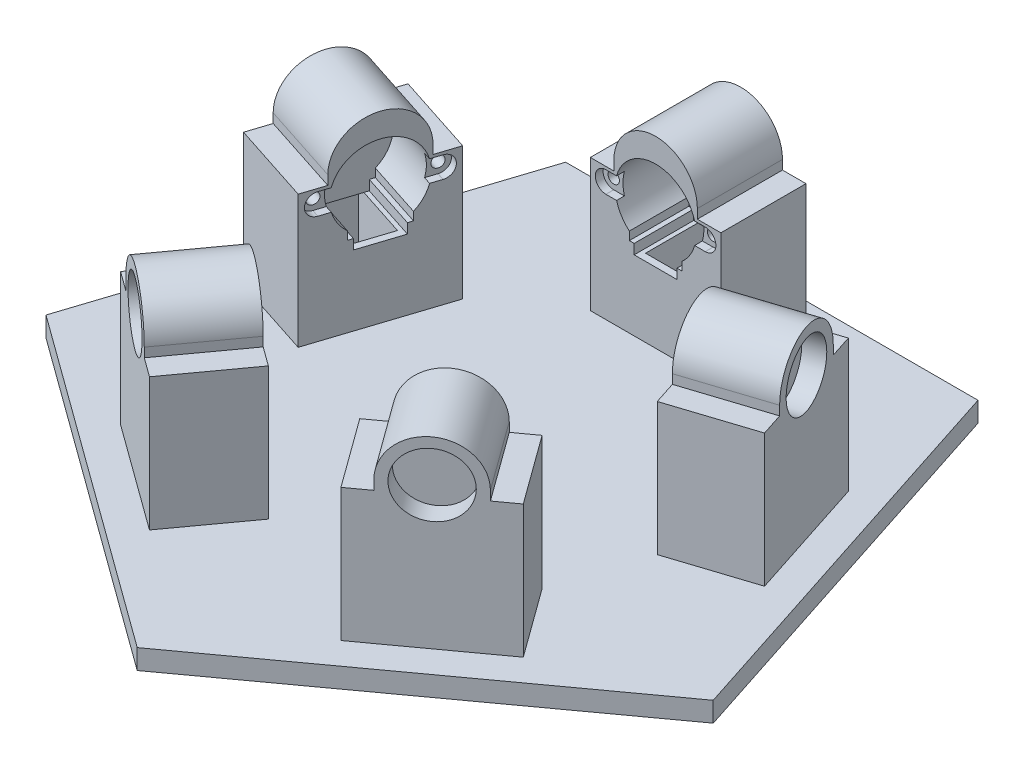
SolidWorks part; units mm, degrees
ref_plane "Front Plane" through (0, 0, 0) normal (0, 0, 1) x (1, 0, 0)
ref_plane "Top Plane" through (0, 0, 0) normal (0, 1, 0) x (1, 0, 0)
ref_plane "Right Plane" through (0, 0, 0) normal (1, 0, 0) x (0, 0, -1)
ref_plane "Psuedo R-offset" through (0, 0, -80) normal (0, 0, 1) x (1, 0, 0)
sketch "Sketch12" plane through (0, 0, 0) normal (0, 1, 0) x (1, 0, 0)
  line L1 (0, -123.6068) -> (117.5571, -38.1966)
  line L2 (117.5571, -38.1966) -> (72.6543, 100)
  line L3 (72.6543, 100) -> (-72.6543, 100)
  line L4 (-72.6543, 100) -> (-117.5571, -38.1966)
  line L5 (-117.5571, -38.1966) -> (0, -123.6068)
  line L6 (-55, 80) -> (55, 80) construction
  circle A0 centre (0, 0) radius 100 construction
  dimension "D1" = 20
extrude "Base" add sketch "Sketch12" against normal blind 7
ref_axis "Axis1" through (0, -9.448, 0) along (0, 1, 0)
sketch "Sketch2" plane through (0, 0, -80) normal (0, 0, 1) x (1, 0, 0)
  line L0 (-7.55, 28.2411) -> (-7.55, 24.75)
  line L1 (-7.55, 24.75) -> (7.55, 24.75)
  line L2 (7.55, 24.75) -> (7.55, 28.2411)
  line L3 (7.55, 28.2411) -> (9.25, 28.2411)
  line L4 (9.25, 28.2411) -> (9.25, 31.1603)
  line L5 (-7.55, 28.2411) -> (-9.25, 28.2411)
  line L6 (-9.25, 28.2411) -> (-9.25, 31.1603)
  line L7 (-14.7095, 50) -> (-23, 50)
  line L8 (-23, 50) -> (-23, 0)
  line L10 (14.7095, 50) -> (23, 50)
  line L11 (23, 50) -> (23, 0)
  line L13 (-23, 0) -> (23, 0)
  line L14 (0, 0) -> (117.5571, 0) construction
  arc A0 (14.7095, 50) -> (-14.7095, 50) centre (0, 50) ccw
  arc A4 (9.25, 31.1603) -> (-9.25, 31.1603) centre (0, 42) ccw
  dimension "D1" = 8.2905
  dimension "D12" = 3.4911
  dimension "D16" = 14.25
  dimension "D17" = 14.7095
  dimension "D2" = 8.2905
  dimension "D3" = 25.25
  dimension "D5" = 50
  dimension "D7" = 46
  dimension "D9" = 2.9191
  dimension "D10" = 1.7
  dimension "D11" = 1.7
  dimension "D13" = 15.1
  dimension "D14" = 2.9191
  dimension "D15" = 3.4911
extrude "Boss-Extrude1" add sketch "Sketch2" along normal blind 20.95
sketch "Sketch3" plane through (0, 0, -80) normal (0, 0, 1) x (1, 0, 0)
  line L7 (-14.7095, 50) -> (-23, 50)
  line L8 (-23, 50) -> (-23, 0)
  line L9 (14.7095, 50) -> (23, 50)
  line L10 (23, 50) -> (23, 0)
  line L11 (-23, 0) -> (23, 0)
  line L12 (23, 50) -> (14.7095, 50) construction
  line L13 (-23, 50) -> (-23, 0) construction
  line L17 (-23, 0) -> (23, 0) construction
  line L19 (23, 0) -> (23, 50) construction
  arc A0 (14.7095, 50) -> (-14.7095, 50) centre (0, 50) ccw
  arc A1 (14.7095, 50) -> (-14.7095, 50) centre (0, 50) ccw construction
  dimension "D1" = 0
extrude "Boss-Extrude2" add sketch "Sketch3" against normal blind 9.05
sketch "Sketch6" plane through (0, 0, -59.05) normal (0, 0, 1) x (1, 0, 0)
  line L0 (-14.7095, 50) -> (-23, 50) construction
  line L1 (-23, 50) -> (-23, 0) construction
  line L2 (23, 50) -> (14.7095, 50) construction
  line L3 (23, 0) -> (23, 50) construction
  circle A0 centre (-17.5, 42) radius 2
  circle A1 centre (17.5, 42) radius 2
  dimension "D1" = 8
  dimension "D2" = 5.5
  dimension "D3" = 4
  dimension "D4" = 8
  dimension "D5" = 5.5
  dimension "D6" = 4
extrude "Cut-Extrude2" cut sketch "Sketch6" against normal blind 10
sketch "Sketch7" plane through (0, 0, -59.05) normal (0, 0, 1) x (1, 0, 0)
  line L0 (-17.5, 42) -> (17.5, 42) construction
  line L3 (-17.5, 45.75) -> (17.5, 45.75)
  line L4 (-17.5, 38.25) -> (17.5, 38.25)
  arc A2 (-17.5, 45.75) -> (-17.5, 38.25) centre (-17.5, 42) ccw
  arc A3 (17.5, 38.25) -> (17.5, 45.75) centre (17.5, 42) ccw
  circle A4 centre (-17.5, 42) radius 2 construction
  circle A5 centre (-17.5, 42) radius 2 construction
  circle A6 centre (17.5, 42) radius 2 construction
  point P2 (0, 42)
  dimension "D2" = 7.5
  dimension "D3" = 1.75
  dimension "D4" = 1.75
  dimension "D1" = 3.75
extrude "Cut-Extrude3" cut sketch "Sketch7" against normal blind 2.75
sketch "Sketch8" plane through (0, 0, -59.05) normal (0, 0, 1) x (1, 0, 0)
  line L0 (-14.7095, 50) -> (-23, 50) construction
  line L1 (-14.7095, 50) -> (-23, 50)
  line L2 (-14.7095, 50) -> (-14.7095, 46.75)
  line L3 (-14.7095, 46.75) -> (-23, 46.75)
  line L4 (-23, 50) -> (-23, 46.75)
  line L5 (14.7095, 50) -> (23, 50)
  line L6 (14.7095, 50) -> (14.7095, 46.75)
  line L7 (14.7095, 46.75) -> (23, 46.75)
  line L8 (23, 50) -> (23, 46.75)
  line L9 (-23, 50) -> (-23, 0) construction
  line L10 (-13.7477, 45.75) -> (-17.5, 45.75) construction
  line L11 (17.5, 45.75) -> (13.7477, 45.75) construction
  line L12 (23, 0) -> (23, 50) construction
  line L13 (23, 50) -> (14.7095, 50) construction
  dimension "D2" = 1
  dimension "D3" = 1
extrude "Cut-Extrude4" cut sketch "Sketch8" along normal through all both and the other way through all
sketch "Sketch11" plane through (0, 0, -89.05) normal (0, 0, -1) x (-1, 0, 0)
  circle A0 centre (0, 50) radius 11.15
  arc A1 (14.7095, 50) -> (-14.7095, 50) centre (0, 50) ccw construction
  dimension "D1" = 22.3
extrude "Bearing Hole" cut sketch "Sketch11" against normal blind 7
sketch "Sketch9" plane through (0, 24.75, -19.25) normal (0, 1, 0) x (-1, 0, 0)
  line L0 (7.55, -39.8) -> (-7.55, -39.8) construction
  line L1 (-6.05, -42.3) -> (6.05, -42.3)
  line L2 (-6.05, -42.3) -> (-6.05, -63.8)
  line L3 (-6.05, -63.8) -> (6.05, -63.8)
  line L4 (6.05, -42.3) -> (6.05, -63.8)
  line L8 (-7.55, -39.8) -> (-7.55, -60.75) construction
  line L9 (7.55, -39.8) -> (7.55, -60.75) construction
  line L10 (7.55, -69.8) -> (-7.55, -69.8) construction
  dimension "D1" = 2.5
  dimension "D2" = 1.5
  dimension "D3" = 1.5
  dimension "D4" = 6
extrude "Wire Hole" cut sketch "Sketch9" against normal blind 20
pattern_circular "CirPattern2" count 5 over 360 about axis through (0, -9.448, 0) along (0, 1, 0) of "Wire Hole", "Bearing Hole", "Cut-Extrude4", "Cut-Extrude3", "Cut-Extrude2", "Boss-Extrude2", "Boss-Extrude1"
ref_plane "R_Offset (measure)" through (0, 0, -74.05) normal (0, 0, 1) x (1, 0, 0)
sketch "Sketch13" plane through (0, 0, 0) normal (0, 1, 0) x (1, 0, 0)
  circle A0 centre (0, 0) radius 5
  dimension "D1" = 10
extrude "Camera Hole" cut sketch "Sketch13" against normal through all
